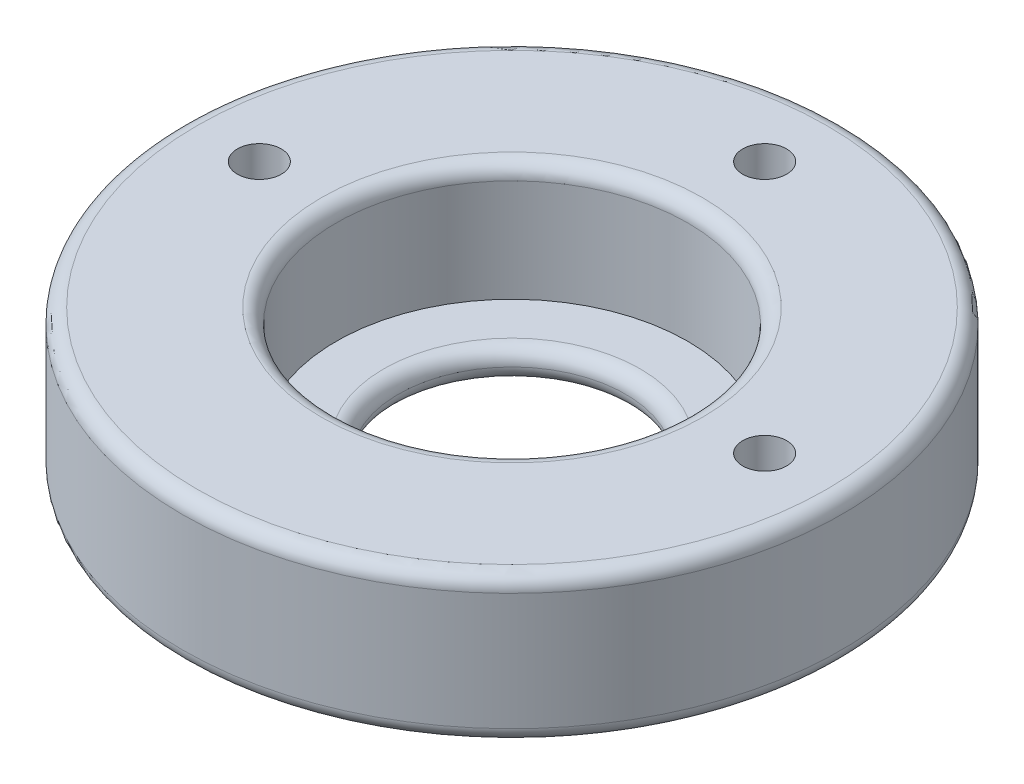
SolidWorks part; units mm, degrees
ref_plane "Front Plane" through (0, 0, 0) normal (0, 0, 1) x (1, 0, 0)
ref_plane "Top Plane" through (0, 0, 0) normal (0, 1, 0) x (1, 0, 0)
ref_plane "Right Plane" through (0, 0, 0) normal (1, 0, 0) x (0, 0, -1)
sketch "Sketch1" plane through (0, 0, 0) normal (0, 1, 0) x (1, 0, 0)
  circle A0 centre (0, 0) radius 22.5
  circle A1 centre (0, 0) radius 17.25
  circle A2 centre (-17.25, 0) radius 1.5
  circle A3 centre (0, 17.25) radius 1.5
  circle A4 centre (17.25, 0) radius 1.5
  dimension "D1" = 45
  dimension "D2" = 34.5
  dimension "D3" = 3
extrude "Boss-Extrude1" add sketch "Sketch1" along normal blind 10 contours A4 A1 A3 A2 | A0 A4 A1 A2 A3 region at (-21.8636, 0, 0) region at (0, 0, 0.0623)
sketch "Sketch2" plane through (0, 10, 0) normal (0, 1, 0) x (1, 0, 0)
  circle A0 centre (0, 0) radius 12
extrude "Cut-Extrude1" cut sketch "Sketch2" against normal blind 8
sketch "Sketch3" plane through (0, 2, 0) normal (0, 1, 0) x (1, 0, 0)
  circle A0 centre (0, 0) radius 7.75
  dimension "D1" = 15.5
extrude "Cut-Extrude2" cut sketch "Sketch3" against normal blind 8
sketch "Sketch4" plane through (0, 0, 0) normal (0, 1, 0) x (1, 0, 0)
  circle A0 centre (-17.25, 0) radius 3
  circle A1 centre (0, 17.25) radius 3
  circle A2 centre (17.25, 0) radius 3
fillet "Fillet1" radius 1 5 edges at (0, 10, 12) (0, 10, 22.5) (0, 2, 7.75) (0, 0, 7.75) (0, 0, 22.5)
extrude "Cut-Extrude4" cut sketch "Sketch4" along normal blind 4 contours A2 | A1 | A0
